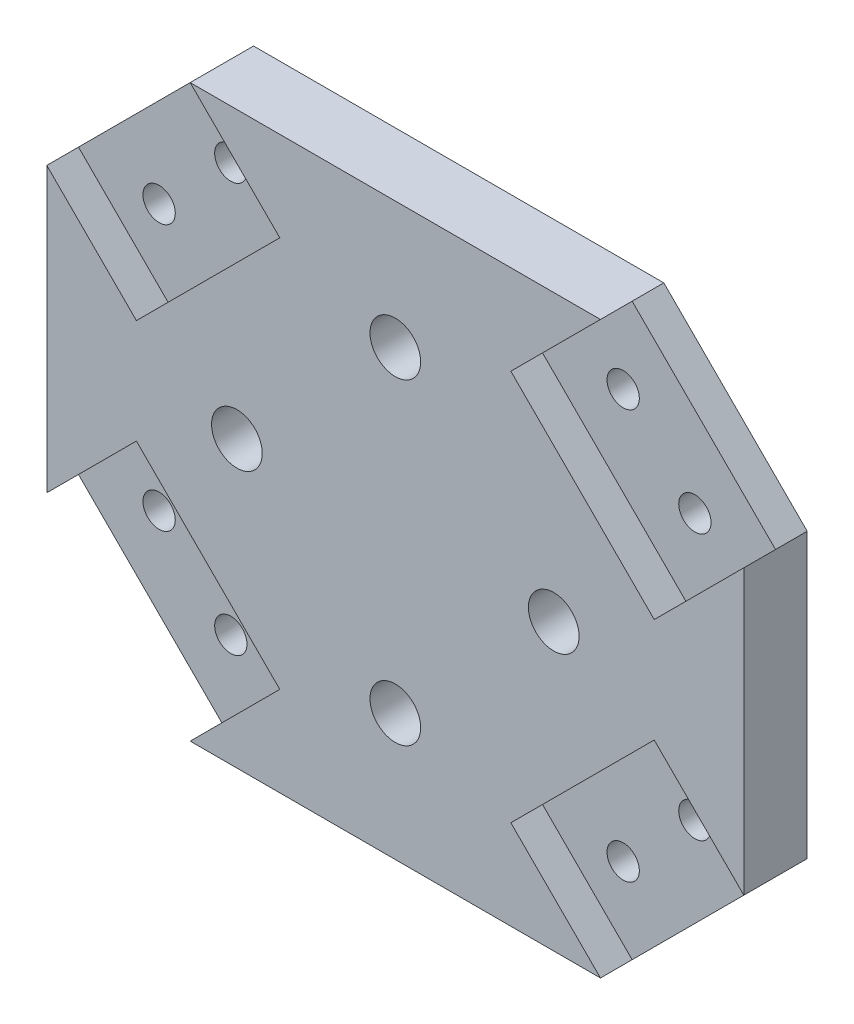
SolidWorks part; units mm, degrees
ref_plane "Plan de face" through (0, 0, 0) normal (0, 0, 1) x (1, 0, 0)
ref_plane "Plan de dessus" through (0, 0, 0) normal (0, 1, 0) x (1, 0, 0)
ref_plane "Plan de droite" through (0, 0, 0) normal (1, 0, 0) x (0, 0, -1)
sketch "Esquisse1" plane through (0, 0, 0) normal (0, 0, 1) x (1, 0, 0)
  line L0 (-55, 22.3726) -> (-32.3726, 45)
  line L1 (55, -45) -> (-55, -45)
  line L2 (55, -45) -> (55, 45)
  line L3 (55, 45) -> (-55, 45)
  line L4 (-55, -45) -> (-55, 45)
  line L5 (55, -45) -> (-55, 45) construction
  line L6 (55, 45) -> (-55, -45) construction
  line L7 (0, -45) -> (0, 45) construction
  line L8 (-55, 0) -> (55, 0) construction
  line L9 (55, 22.3726) -> (32.3726, 45)
  line L10 (55, -22.3726) -> (32.3726, -45)
  line L11 (-55, -22.3726) -> (-32.3726, -45)
  circle A4 centre (0, 25) radius 4
  circle A5 centre (25, 0) radius 4
  circle A6 centre (0, -25) radius 4
  circle A7 centre (-25, 0) radius 4
  point P0 (0, 0)
  point P23 (0, 0)
  point P26 (0, 0)
  point P29 (0, 0)
  point P32 (0, 0)
  dimension "D5" = 8
  dimension "D6" = 25
  dimension "D1" = 90
  dimension "D2" = 110
  dimension "D3" = 32
  dimension "D4" = 45
  dimension "D7" = 4
extrude "Boss.-Extru.1" add sketch "Esquisse1" along normal blind 10 contours L4 L11 L1 L10 L2 L9 L3 L0 A5 A4 region at (0, 0, 0)
sketch "Esquisse3" plane through (0, 0, 10) normal (0, 0, 1) x (1, 0, 0)
  line L0 (-55, 22.3726) -> (-32.3726, 45)
  line L1 (-32.3726, 45) -> (-18.2304, 30.8579)
  line L2 (-18.2304, 30.8579) -> (-40.8579, 8.2304)
  line L3 (-40.8579, 8.2304) -> (-55, 22.3726)
  line L4 (-55, 22.3726) -> (-32.3726, 45) construction
  point P2 (0, 0)
  point P7 (-43.6863, 33.6863)
  dimension "D1" = 20
extrude "Enlèv. mat.-Extru.1" cut sketch "Esquisse3" against normal blind 5
sketch "Esquisse4" plane through (0, 0, 5) normal (0, 0, 1) x (1, 0, 0)
  line L0 (-43.6863, 33.6863) -> (-29.5442, 19.5442) construction
  line L1 (-32.3726, 45) -> (-55, 22.3726) construction
  line L3 (-47.9289, 15.3015) -> (-36.6152, 26.6152) construction
  line L5 (-55, 22.3726) -> (-40.8579, 8.2304) construction
  line L6 (-40.8579, 8.2304) -> (-18.2304, 30.8579) construction
  line L7 (-32.3726, 45) -> (-55, 22.3726) construction
  circle A0 centre (-42.2721, 20.9584) radius 2.55
  circle A1 centre (-30.9584, 32.2721) radius 2.55
  point P4 (-29.679, 19.7177)
  dimension "D1" = 5.1
  dimension "D2" = 32
  dimension "D3" = 20
extrude "Enlèv. mat.-Extru.2" cut sketch "Esquisse4" against normal through all
mirror "Symétrie1" about plane through (0, 0, 0) normal (1, 0, 0) of "Enlèv. mat.-Extru.2", "Enlèv. mat.-Extru.1" second plane through (0, 0, 0) second plane normal (0, 1, 0)
